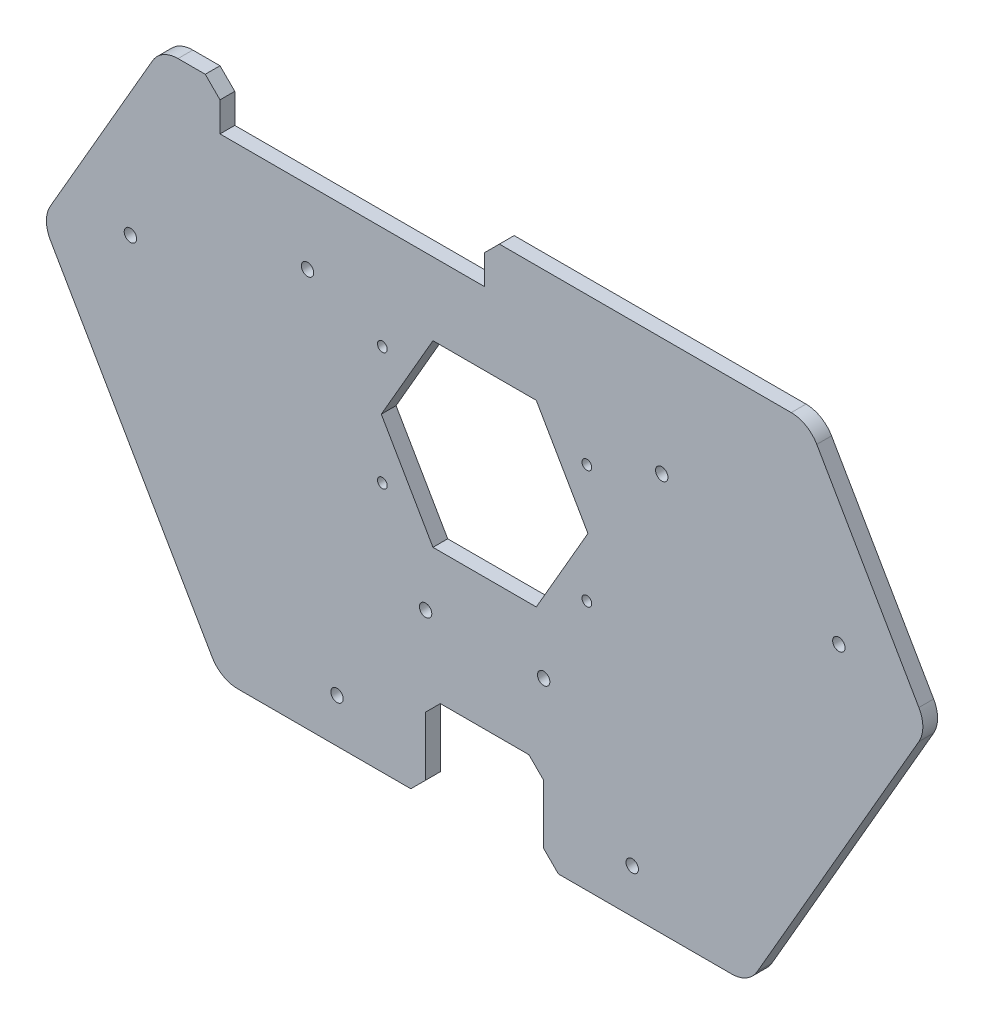
SolidWorks part; units mm, degrees
material "5052-O"
ref_plane "前基準面" through (0, 0, 0) normal (0, 0, 1) x (1, 0, 0)
ref_plane "上基準面" through (0, 0, 0) normal (0, 1, 0) x (1, 0, 0)
ref_plane "右基準面" through (0, 0, 0) normal (1, 0, 0) x (0, 0, -1)
sketch "草圖1" plane through (0, 0, 0) normal (0, 0, 1) x (1, 0, 0)
  line L1 (150, 0) -> (75, 129.9038)
  line L2 (75, 129.9038) -> (-75, 129.9038)
  line L3 (-75, 129.9038) -> (-150, 0)
  line L4 (-150, 0) -> (-75, -129.9038)
  line L5 (-75, -129.9038) -> (75, -129.9038)
  line L6 (75, -129.9038) -> (150, 0)
  circle A0 centre (0, 0) radius 129.9038 construction
  dimension "D1" = 150
extrude "填料-伸長1" add sketch "草圖1" along normal blind 5
ref_axis "基準軸1" through (0, 0, 0) along (0, 0, 1)
sketch "草圖3" plane through (0, 0, 5) normal (0, 0, 1) x (1, 0, 0)
  line L0 (-109.641, 69.9038) -> (-89.641, 69.9038)
  line L1 (-75, 129.9038) -> (-150, 0) construction
  line L2 (-89.641, 69.9038) -> (-89.641, 54.9038)
  line L3 (-89.641, 54.9038) -> (0, 54.9038)
  line L4 (0, 54.9038) -> (0, 69.9038)
  line L5 (0, 69.9038) -> (109.641, 69.9038)
  line L6 (150, 0) -> (75, 129.9038) construction
  line L7 (75, 129.9038) -> (-75, 129.9038) construction
  point P16 (0, 129.9038)
  dimension "D1" = 75
  dimension "D2" = 15
  dimension "D4" = 20
extrude "除料-伸長2" cut sketch "草圖3" against normal through all and the other way through all
sketch "草圖4" plane through (0, 0, 5) normal (0, 0, 1) x (1, 0, 0)
  line L1 (35, 0) -> (17.5, 30.3109)
  line L2 (17.5, 30.3109) -> (-17.5, 30.3109)
  line L3 (-17.5, 30.3109) -> (-35, 0)
  line L4 (-35, 0) -> (-17.5, -30.3109)
  line L5 (-17.5, -30.3109) -> (17.5, -30.3109)
  line L6 (17.5, -30.3109) -> (35, 0)
  circle A0 centre (0, 0) radius 30.3109 construction
  dimension "D1" = 35
extrude "除料-伸長3" cut sketch "草圖4" against normal up to next
chamfer "導角1" distance 5 angle 45 2 edges at (0, 69.9038, 2.5) (-89.641, 69.9038, 2.5)
sketch "草圖5" plane through (0, 0, 5) normal (0, 0, 1) x (1, 0, 0)
  line L0 (-89.4338, -104.9038) -> (-20, -104.9038)
  line L1 (-150, 0) -> (-75, -129.9038) construction
  line L2 (-20, -104.9038) -> (-20, -74.9038)
  line L3 (-20, -74.9038) -> (20, -74.9038)
  line L4 (20, -74.9038) -> (20, -104.9038)
  line L5 (20, -104.9038) -> (89.4338, -104.9038)
  line L6 (75, -129.9038) -> (150, 0) construction
  line L7 (-75, -129.9038) -> (75, -129.9038) construction
  dimension "D1" = 25
  dimension "D2" = 30
  dimension "D3" = 40
extrude "除料-伸長6" cut sketch "草圖5" against normal through all and the other way through all flip side to cut
chamfer "導角2" distance 5 angle 45 4 edges at (20, -104.9038, 2.5) (20, -74.9038, 2.5) (-20, -74.9038, 2.5) (-20, -104.9038, 2.5)
sketch "草圖6" plane through (0, 0, 5) normal (0, 0, 1) x (1, 0, 0)
  circle A0 centre (-50, -90) radius 2.1
  circle A1 centre (-120, 10) radius 2.1
  circle A2 centre (-60, 30) radius 2.1
  circle A3 centre (-20, -50) radius 2.1
  dimension "D1" = 4.2
  dimension "D2" = 4.2
  dimension "D7" = 4.2
  dimension "D8" = 4.2
  dimension "D3" = 50
  dimension "D4" = 90
  dimension "D5" = 120
  dimension "D6" = 10
  dimension "D9" = 50
  dimension "D10" = 20
  dimension "D11" = 30
  dimension "D12" = 60
extrude "除料-伸長7" cut sketch "草圖6" against normal up to next
mirror "鏡射1" about plane through (0, 0, 0) normal (1, 0, 0) of "除料-伸長7"
fillet "圓角1" radius 10 6 edges at (109.641, 69.9038, 2.5) (150, 0, 2.5) (89.4338, -104.9038, 2.5) (-89.4338, -104.9038, 2.5) (-150, 0, 2.5) (-109.641, 69.9038, 2.5)
sketch "草圖8" plane through (0, 0, 5) normal (0, 0, 1) x (1, 0, 0)
  line L0 (-26.25, 15.1554) -> (-34.641, 20) construction
  line L1 (-34.641, 20) -> (34.641, 20) construction
  line L2 (-34.641, 20) -> (-34.641, -20) construction
  line L3 (-34.641, -20) -> (34.641, -20) construction
  line L4 (34.641, 20) -> (34.641, -20) construction
  line L5 (-17.5, 30.3109) -> (-35, 0) construction
  circle A1 centre (0, 0) radius 40 construction
  dimension "D1" = 80
hole_wizard "M4x0.7 螺紋孔1" positions "草圖9" profile "草圖10" tap size "M4x0.7" standard "Ansi Metric"
sketch "草圖9" plane through (0, 0, 5) normal (0, 0, 1) x (1, 0, 0)
  point P0 (-34.641, 20)
  point P3 (34.641, 20)
  point P6 (34.641, -20)
  point P9 (-34.641, -20)
sketch "草圖10" plane through (-34.641, 20, 5) normal (1, 0, 0) x (0, -1, 0)
  line L0 (0, 0) -> (0, 12.4914)
  line L1 (0, 12.4914) -> (1.65, 11.5)
  line L2 (1.65, 11.5) -> (1.65, 0)
  line L5 (1.65, 0) -> (0, 0)
  line L10 (0, 12.4914) -> (-1.65, 11.5) construction
  line L11 (0, -6.35) -> (0, 107.95) construction
  dimension "螺孔鑽直徑" = 3.3
  dimension "螺孔鑽深度" = 11.5
  dimension "導頭角度" = 118
cosmetic thread "鑽孔螺紋1" parameters "D1"=8, "D2"=4
cosmetic thread "鑽孔螺紋2" parameters "D1"=8, "D2"=4
cosmetic thread "鑽孔螺紋3" parameters "D1"=8, "D2"=4
cosmetic thread "鑽孔螺紋4" parameters "D1"=8, "D2"=4
